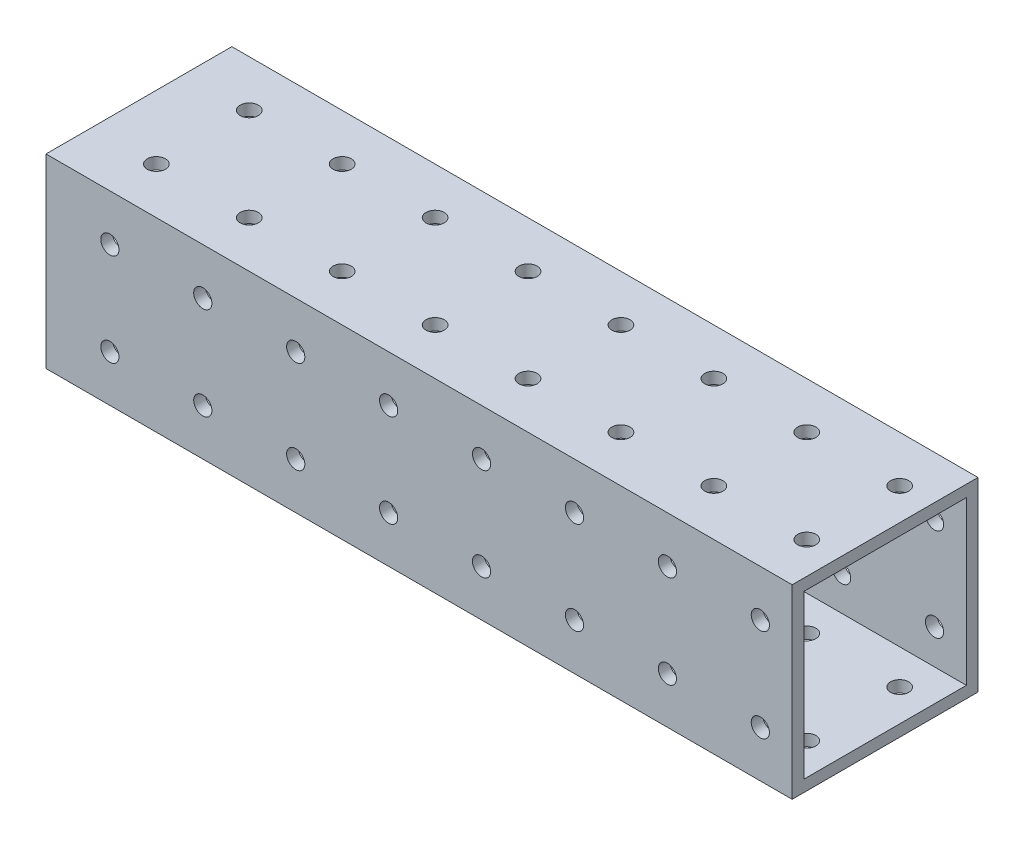
SolidWorks part; units mm, degrees
material "6061-T6 (SS)"
ref_plane "Front Plane" through (0, 0, 0) normal (0, 0, 1) x (1, 0, 0)
ref_plane "Top Plane" through (0, 0, 0) normal (0, 1, 0) x (1, 0, 0)
ref_plane "Right Plane" through (0, 0, 0) normal (1, 0, 0) x (0, 0, -1)
sketch "Sketch1" plane through (0, 0, 0) normal (1, 0, 0) x (0, 0, -1)
  line L1 (0, 0) -> (50.8, 0)
  line L2 (0, 0) -> (0, 50.8)
  line L3 (0, 50.8) -> (50.8, 50.8)
  line L4 (50.8, 0) -> (50.8, 50.8)
  dimension "D1" = 50.8
extrude "Boss-Extrude1" add sketch "Sketch1" along normal blind 203.9681
shell "Shell1" thickness 3.175 removed face at (0, 25.4, -25.4) removed face at (203.9681, 25.4, -25.4)
sketch "Sketch2" plane through (0, 0, -50.8) normal (0, 0, -1) x (-1, 0, 0)
  line L0 (-195.2625, 0) -> (-195.2625, 50.8) construction
  line L1 (-203.9681, 0) -> (0, 0) construction
  line L2 (-203.9681, 50.8) -> (0, 50.8) construction
  line L3 (-203.9681, 0) -> (-203.9681, 50.8) construction
  circle A22 centre (-195.2625, 38.1) radius 2.4892
  circle A23 centre (-195.2625, 12.7) radius 2.4892
  dimension "D2" = 4.9784
  dimension "D3" = 25.4
  dimension "D4" = 12.7
  dimension "D1" = 8.7056
extrude "Cut-Extrude3" cut sketch "Sketch2" against normal through all
sketch "Sketch3" plane through (0, 0, 0) normal (0, -1, 0) x (1, 0, 0)
  line L0 (195.2625, 0) -> (195.2625, -50.8) construction
  line L1 (203.9681, 0) -> (0, 0) construction
  line L2 (203.9681, -50.8) -> (0, -50.8) construction
  line L5 (203.9681, -50.8) -> (203.9681, 0) construction
  circle A2 centre (195.2625, -12.7) radius 2.4892
  circle A3 centre (195.2625, -38.1) radius 2.4892
  dimension "D1" = 4.9784
  dimension "D2" = 12.7
  dimension "D3" = 25.4
  dimension "D4" = 8.7056
extrude "Cut-Extrude2" cut sketch "Sketch3" against normal through all
pattern_linear "LPattern1" count 8 spacing 25.4 along (-1, 0, 0) of "Cut-Extrude2", "Cut-Extrude3"
